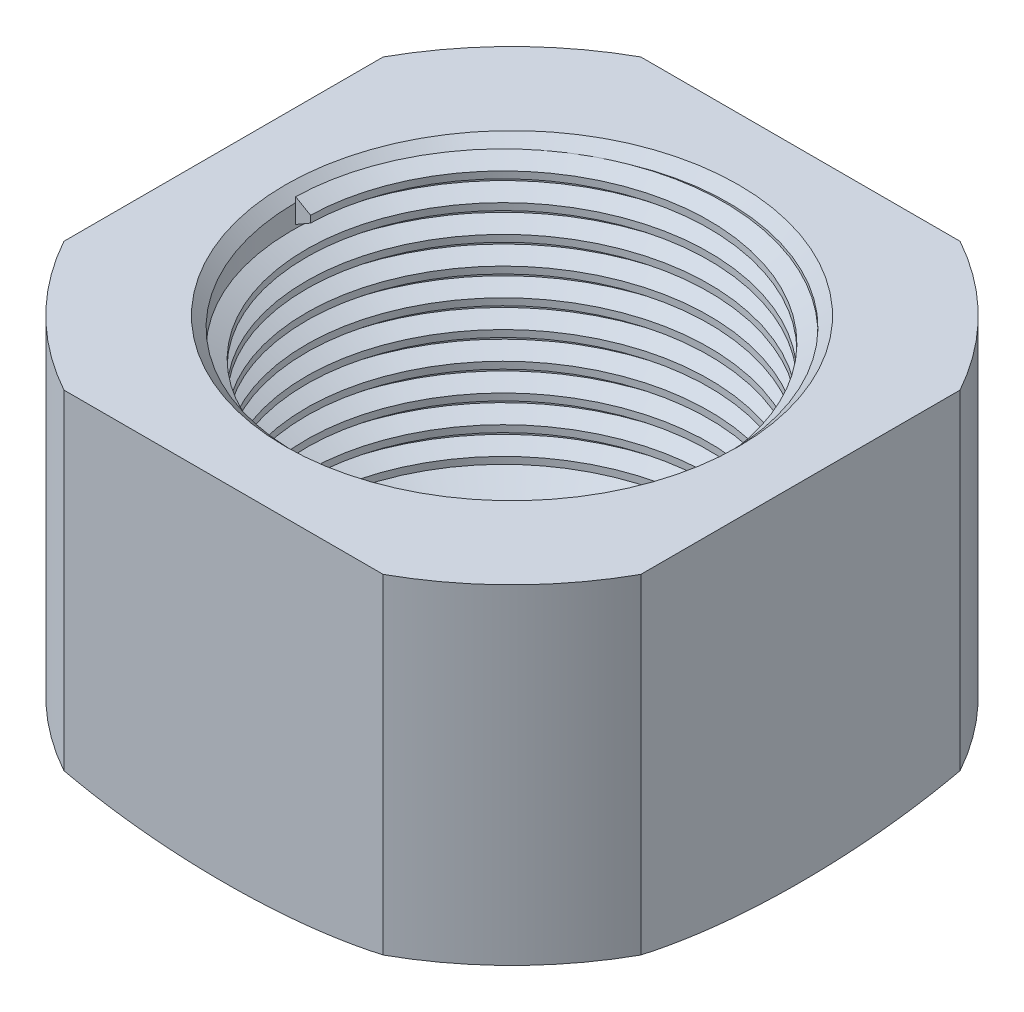
SolidWorks part; units mm, degrees
material "Plain Carbon Steel"
ref_plane "Front Plane" through (0, 0, 0) normal (0, 0, 1) x (1, 0, 0)
ref_plane "Top Plane" through (0, 0, 0) normal (0, 1, 0) x (1, 0, 0)
ref_plane "Right Plane" through (0, 0, 0) normal (1, 0, 0) x (0, 0, -1)
sketch "Sketch1" plane through (0, 0, 0) normal (0, 0, 1) x (1, 0, 0)
  line L0 (0, 0) -> (25.4, 0) construction
  line L1 (25.4, 0) -> (25.4, 28.575) construction
  line L2 (25.4, 28.575) -> (16.6687, 28.575)
  line L3 (16.6687, 28.575) -> (16.6687, 7.3619)
  line L5 (0, 53.4636) -> (0, 0) construction
  line L6 (25.4, 28.575) -> (25.4, 3.175)
  line L10 (0, 53.4636) -> (0, 0) construction
  line L11 (11.1125, 3.175) -> (11.1125, 0)
  line L12 (11.1125, 3.175) -> (16.6687, 7.3619)
  arc A3 (11.1125, 0) -> (25.4, 3.175) centre (11.1125, 33.7344) ccw
  dimension "D1" = 25.4
  dimension "D2" = 25.4
  dimension "D3" = 37
  dimension "D4" = 16.6687
  dimension "D5" = 11.1125
  dimension "D6" = 3.175
revolve "Revolve1" add sketch "Sketch1" angle 360 about L5
chamfer "Chamfer1" distance 0.7937 angle 45 1 edges at (-16.6687, 28.575, 0)
thread "Thread1" pitch 2.1167 method extrude profile "Thread Profile2" start angle 0, offset 0.3969, length 20.32, pitch 2.1167, diameter 33.3375
ref_plane "Plane2" through (-16.6687, 28.1781, 0) normal (0, 0, 1) x (-1, 0, 0)
sketch "Thread Profile2" plane through (-16.6687, 28.1781, 0) normal (0, 0, 1) x (-1, 0, 0)
  line L0 (0, 0) -> (0, 2.1167) construction
  line L11 (0, 0) -> (0, 1.8521)
  line L12 (0, 1.8521) -> (-1.1457, 1.1906)
  line L13 (-1.1457, 1.1906) -> (-1.1457, 0.6615)
  line L15 (-1.1457, 0.6615) -> (0, 0)
  line L17 (-1.1457, 0.926) -> (0, 0.926) construction
  point P2 (0, 0)
  dimension "Pitch" = 2.1167
  dimension "Profile_Angle" = 60
  dimension "Profile_Land" = 0.5292
  dimension "Profile_Height" = 1.1457
sketch "Sketch7" plane through (0, 0, 0) normal (0, 1, 0) x (1, 0, 0)
  circle A0 centre (0, 0) radius 11.1125
  ellipse E0 centre (0, 0) end of major axis (-11.1125, 0) minor radius 9.525 construction
  dimension "D1" = 22.225
  dimension "D2" = 19.05
sketch "Sketch8" plane through (0, 28.575, 0) normal (0, 1, 0) x (1, 0, 0)
  line L0 (-22.225, 12.2967) -> (-22.225, -12.2967)
  circle A0 centre (0, 0) radius 25.4 construction
  arc A1 (-22.225, -12.2967) -> (-22.225, 12.2967) centre (0, 0) cw
  point P5 (-22.225, 0)
  point P6 (-25.4, 0)
  dimension "D1" = 3.175
extrude "Cut-Extrude1" cut sketch "Sketch8" against normal through all
pattern_circular "CirPattern1" count 4 over 360 about axis through (0, 28.575, 0) along (0, 1, 0) of "Cut-Extrude1"
